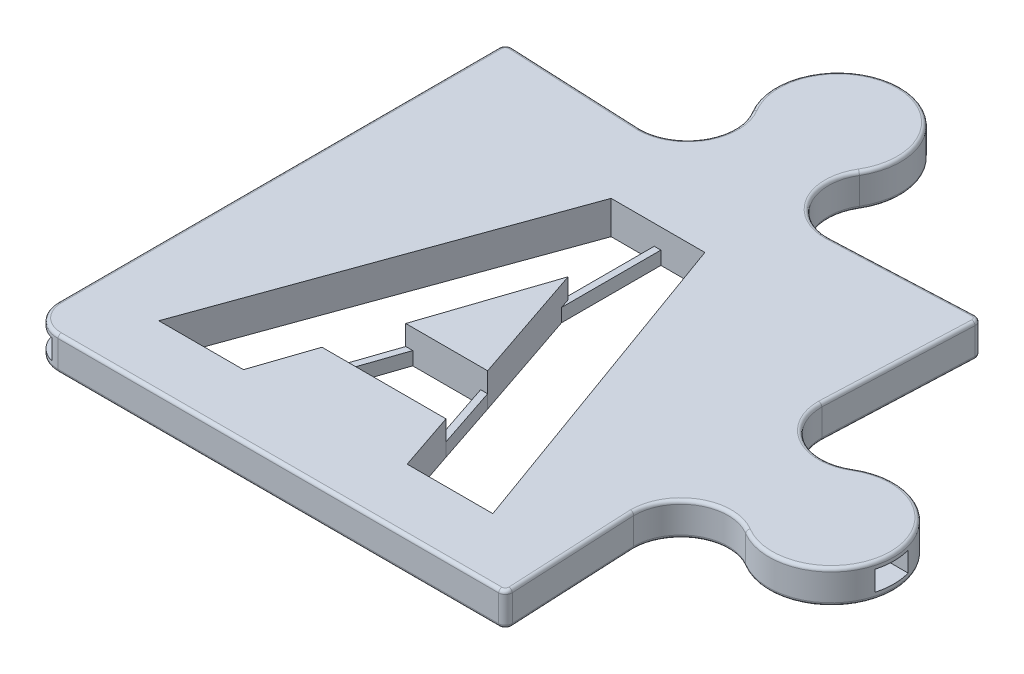
SolidWorks part; units mm, degrees
ref_plane "Front Plane" through (0, 0, 0) normal (0, 0, 1) x (1, 0, 0)
ref_plane "Top Plane" through (0, 0, 0) normal (0, 1, 0) x (1, 0, 0)
ref_plane "Right Plane" through (0, 0, 0) normal (1, 0, 0) x (0, 0, -1)
sketch "Sketch1" plane through (0, 0, 0) normal (0, 1, 0) x (1, 0, 0)
  line L0 (-31, -36) -> (37, -36) construction
  line L1 (-36, 37) -> (-36, -31) construction
  line L2 (-14.1421, 36) -> (-36, 37) construction
  line L3 (37, 37) -> (14.1421, 36) construction
  line L4 (36, 13.1421) -> (37, 37) construction
  line L5 (37, -36) -> (36, -15.1421) construction
  line L6 (-35.4, 36.3719) -> (-35.4, -31)
  line L7 (-36, 36) -> (36, 36) construction
  line L8 (-36, 36) -> (-36, -36) construction
  line L9 (-36, -36) -> (36, -36) construction
  line L10 (36, 36) -> (36, -36) construction
  line L11 (-31, -35.4) -> (36.3705, -35.4)
  line L12 (36.3705, -35.4) -> (35.4, -15.1568)
  line L13 (35.4, 13.155) -> (36.3732, 36.372)
  line L14 (36.3732, 36.372) -> (14.1555, 35.4)
  line L15 (-14.1562, 35.4) -> (-35.4, 36.3719)
  line L16 (-30, -24) -> (30, -24) construction
  line L17 (-30, 29) -> (30, 29) construction
  line L18 (-30, 29) -> (-30, -31) construction
  line L19 (-30, -31) -> (30, -31) construction
  line L20 (30, 29) -> (30, -31) construction
  line L21 (-30, 24) -> (30, 24) construction
  line L22 (-30, 24) -> (-30, -26) construction
  line L23 (-30, -26) -> (30, -26) construction
  line L24 (30, 24) -> (30, -26) construction
  arc A0 (-36, -31) -> (-31, -36) centre (-31, -31) ccw construction
  arc A1 (-14.1421, 36) -> (-8.571, 45.8485) centre (-14.1421, 42.5) ccw construction
  arc A2 (8.571, 45.8485) -> (-8.571, 45.8485) centre (0, 51) ccw construction
  arc A3 (8.571, 45.8485) -> (14.1421, 36) centre (14.1421, 42.5) ccw construction
  arc A4 (36, 13.1421) -> (45.8485, 7.571) centre (42.5, 13.1421) ccw construction
  arc A5 (45.8485, -9.571) -> (45.8485, 7.571) centre (51, -1) ccw construction
  arc A6 (45.8485, -9.571) -> (36, -15.1421) centre (42.5, -15.1421) ccw construction
  arc A7 (-35.4, -31) -> (-31, -35.4) centre (-31, -31) ccw
  arc A8 (46.1576, -9.0567) -> (35.4, -15.1568) centre (42.5, -15.1421) ccw
  arc A9 (46.1576, -9.0567) -> (46.1576, 7.0567) centre (51, -1) ccw
  arc A10 (35.4, 13.155) -> (46.1576, 7.0567) centre (42.5, 13.1421) ccw
  arc A11 (8.0567, 46.1576) -> (14.1555, 35.4) centre (14.1421, 42.5) ccw
  arc A12 (8.0567, 46.1576) -> (-8.0567, 46.1576) centre (0, 51) ccw
  arc A13 (-14.1562, 35.4) -> (-8.0567, 46.1576) centre (-14.1421, 42.5) ccw
  point P32 (36, 0)
  point P34 (0, 36)
  dimension "D5" = 6.5
  dimension "D6" = 10
  dimension "D7" = 6.5
  dimension "D13" = 5
  dimension "D9" = 10
  dimension "D11" = 6.5
  dimension "D12" = 6.5
  dimension "D1" = 72
  dimension "D2" = 1
  dimension "D3" = 1
  dimension "D4" = 15
  dimension "D8" = 1
  dimension "D10" = 35
  dimension "D14" = 15
  dimension "D15" = 36
  dimension "D16" = 1
  dimension "D18" = 60
  dimension "D19" = 60
  dimension "D20" = 5
  dimension "D21" = 6
  dimension "D22" = 5
  dimension "D23" = 50
  dimension "D24" = 2
  dimension "D17" = 0.6
extrude "Boss-Extrude1" add sketch "Sketch1" along normal blind 5
sketch "Sketch6" plane through (0, 0, 0) normal (0, -1, 0) x (1, 0, 0)
  line L0 (-35.4, -36.3719) -> (-35.4, 31) construction
  line L1 (-35.4, 17.9) -> (-27.4, 17.9)
  line L2 (-35.4, 17.9) -> (-35.4, -16.1)
  line L3 (-35.4, -16.1) -> (-27.4, -16.1)
  line L4 (-27.4, 17.9) -> (-27.4, -16.1)
  line L5 (-31, 35.4) -> (36.3705, 35.4) construction
  line L6 (-35.4, 14.65) -> (-30.4, 14.65)
  line L7 (-35.4, 14.65) -> (-35.4, -12.85)
  line L8 (-35.4, -12.85) -> (-30.4, -12.85)
  line L9 (-30.4, 14.65) -> (-30.4, -12.85)
  point P15 (-27.4, 0.9)
  point P16 (-30.4, 0.9)
  line M28 (-35.4, 31) -> (-35.4, -36.3719)
  dimension "D1" = 8
  dimension "D2" = 20.75
  dimension "D3" = 27.5
  dimension "D4" = 5
  dimension "D5" = 34
extrude "Cut-Extrude3" cut sketch "Sketch6" against normal blind 3 from offset 1 contours L6 L9 L8 L3 L4 L1 M28 | L9 L6 L2 L8 region at (-29.8665, 0, 0.9) region at (-32.9, 0, 0.9) offset against normal yes
extrude "Cut-Extrude4" cut sketch "Sketch6<3>" against normal up to next contours L9 L6 L2 L8 region at (-32.9, 0, 0.9)
sketch "Sketch6<3>" plane through (0, 0, 0) normal (0, -1, 0) x (1, 0, 0) same geometry as "Sketch6"
sketch "Sketch8" plane through (0, 0, 0) normal (0, -1, 0) x (1, 0, 0)
  line L1 (-2.5, -51.4) -> (2.5, -51.4)
  line L2 (-2.5, -51.4) -> (-2.5, -60.4)
  line L3 (-2.5, -60.4) -> (2.5, -60.4)
  line L4 (2.5, -51.4) -> (2.5, -60.4)
  line L5 (51.4, 3.5) -> (60.4, 3.5)
  line L6 (51.4, 3.5) -> (51.4, -1.5)
  line L7 (51.4, -1.5) -> (60.4, -1.5)
  line L8 (60.4, 3.5) -> (60.4, -1.5)
  arc A0 (-8.0567, -46.1576) -> (8.0567, -46.1576) centre (0, -51) ccw construction
  arc A1 (46.1576, -7.0567) -> (46.1576, 9.0567) centre (51, 1) ccw construction
  point P4 (0, -60.4)
  point P13 (60.4, 1)
  dimension "D1" = 5
  dimension "D2" = 9
  dimension "D3" = 5
  dimension "D4" = 9
extrude "Cut-Extrude5" cut sketch "Sketch8" against normal blind 3 from offset 1 offset against normal yes
sketch "Sketch9" plane through (0, 0, 0) normal (0, -1, 0) x (1, 0, 0)
  line L0 (-31, 35.4) -> (36.3705, 35.4) construction
  line L1 (-35.4, 14.65) -> (-35.4, 31) construction
  line L2 (-31.7636, 35.3332) -> (-35.4, 31) construction
  line L3 (-33.2571, 29.735) -> (-30.0429, 33.565) construction
  line L4 (-30.0429, 33.565) -> (-33.2571, 29.735) construction
  line L5 (-30.0429, 33.565) -> (-32.7119, 35.8048)
  line L6 (-33.2571, 29.735) -> (-35.926, 31.9747)
  line L7 (-32.7119, 35.8048) -> (-35.926, 31.9747)
  circle A0 centre (-31.65, 31.65) radius 2.5
  arc A1 (-31, 35.4) -> (-35.4, 31) centre (-31, 31) ccw construction
  arc M41 (-31, 35.4) -> (-35.4, 31) centre (-31, 31) ccw
  dimension "D1" = 5
  dimension "D3" = 3.75
  dimension "D4" = 5.6569
  dimension "D2" = 3.75
extrude "Cut-Extrude6" cut sketch "Sketch9" against normal blind 3 from offset 1 contours A0 L5 L6 M41 | A0 L5 region at (-33.6239, 0, 33.3064) region at (-31.65, 0, 31.65) offset against normal yes
sketch "Sketch11" plane through (-35.4, 0, 0) normal (-1, 0, 0) x (0, 0, 1)
  line L0 (-13.155, 0) -> (-36.372, 0) construction
  line L1 (-25.1, 3) -> (-19.1, 3)
  line L2 (-25.1, 3) -> (-25.1, 1.5)
  line L3 (-25.1, 1.5) -> (-19.1, 1.5)
  line L4 (-19.1, 3) -> (-19.1, 1.5)
  line L5 (-16.1, 4) -> (-16.1, 1) construction
  line L6 (35.4, 0) -> (15.1568, 0) construction
  line L7 (20.9, 3) -> (26.9, 3)
  line L8 (20.9, 3) -> (20.9, 1.5)
  line L9 (20.9, 1.5) -> (26.9, 1.5)
  line L10 (26.9, 3) -> (26.9, 1.5)
  line L12 (17.9, 4) -> (17.9, 1) construction
  dimension "D1" = 3
  dimension "D2" = 1.5
  dimension "D3" = 3
  dimension "D4" = 6
  dimension "D5" = 3
  dimension "D6" = 1.5
  dimension "D7" = 6
  dimension "D8" = 3
fillet "Fillet1" radius 0.5 17 edges at (-35.4, 0, 22.825) (-34.1113, 0, 34.1113) (2.6853, 0, 35.4) (35.8853, 0, 25.2784) (38.9978, 0, 8.966) (60.4, 0, 1) (38.9986, 0, -6.9655) (35.8866, 0, -24.7635) (25.2643, 0, -35.886) (7.9657, 0, -38.9984) (0, 0, -60.4) (-7.9658, 0, -38.9981) (-24.7781, 0, -35.886) (-35.4, 0, -24.611) (-32.9, 0, -12.85) (-30.4, 0, 0.9) (-32.9, 0, 14.65)
fillet "Fillet2" radius 0.5 13 edges at (-7.9658, 5, -38.9981) (0, 5, -60.4) (7.9657, 5, -38.9984) (25.2643, 5, -35.886) (35.8866, 5, -24.7635) (38.9986, 5, -6.9655) (60.4, 5, 1) (38.9978, 5, 8.966) (35.8853, 5, 25.2784) (2.6853, 5, 35.4) (-34.1113, 5, 34.1113) (-35.4, 5, -2.686) (-24.7781, 5, -35.886)
fillet "Fillet3" radius 1 9 edges at (36.2202, 0.1464, -36.2187) (36.2202, 4.8536, -36.2187) (36.3732, 2.5, -36.372) (-35.2536, 0.1464, -36.2186) (-35.2536, 4.8536, -36.2186) (36.2169, 0.1464, 35.2536) (36.2169, 4.8536, 35.2536) (36.3705, 2.5, 35.4) (-35.4, 2.5, -36.3719)
extrude "Cut-Extrude9" cut sketch "Sketch11" against normal blind 3
chamfer "Chamfer1" distance 1 angle 50 2 edges at (-35.4, 1.5, 23.9) (-35.4, 1.5, -22.1) first distance on face at (-35.4, 2.25, -22.1)
sketch "Sketch12" plane through (0, 5, 0) normal (0, 1, 0) x (1, 0, 0)
  text T0 "A" font "Poppins" height 50
extrude "Cut-Extrude10" cut sketch "Sketch12" against normal blind 10
sketch "Sketch13" plane through (0, 0, 0) normal (0, -1, 0) x (1, 0, 0)
  line L0 (-0.1649, -10.5416) -> (-6.2964, 7.7704) construction
  line L1 (-0.6624, -9.0558) -> (0.3376, -9.0558)
  line L2 (-0.6624, -9.0558) -> (-0.6624, -24)
  line L3 (-0.6624, -24) -> (0.3376, -24)
  line L4 (0.3376, -9.0558) -> (0.3376, -24)
  line L5 (-30, -24) -> (30, -24) construction
  line L6 (-9.5012, 17.1686) -> (-12.4897, 26) construction
  line L7 (-25.237, 26) -> (-12.1513, 26)
  line L8 (-25.237, 26) -> (-25.237, 25)
  line L9 (-25.237, 25) -> (-12.1513, 25)
  line L10 (-12.1513, 26) -> (-12.1513, 25)
  line L11 (12.1496, 26) -> (9.1612, 17.1686) construction
  line L12 (25.0412, 26) -> (11.8112, 26)
  line L13 (25.0412, 26) -> (25.0412, 25)
  line L14 (25.0412, 25) -> (11.8112, 25)
  line L15 (11.8112, 26) -> (11.8112, 25)
  line L16 (-9.5012, 17.1686) -> (-6.2964, 7.7704)
  line L17 (-6.2964, 7.7704) -> (-5.2398, 7.7704)
  line L18 (-6.2964, 7.7704) -> (6.0284, 7.7704) construction
  line L19 (-5.2398, 7.7704) -> (-8.4447, 17.1686)
  line L20 (9.1612, 17.1686) -> (-9.5012, 17.1686) construction
  line L21 (-8.4447, 17.1686) -> (-9.5012, 17.1686)
  line L22 (9.1612, 17.1686) -> (6.0284, 7.7704)
  line L23 (6.0284, 7.7704) -> (4.9743, 7.7704)
  line L24 (4.9743, 7.7704) -> (8.1071, 17.1686)
  line L25 (8.1071, 17.1686) -> (9.1612, 17.1686)
  line L26 (6.0284, 7.7704) -> (-0.1649, -10.5416) construction
  dimension "D1" = 1
  dimension "D2" = 1
  dimension "D3" = 1
  dimension "D4" = 1
  dimension "D5" = 1
extrude "Boss-Extrude2" add sketch "Sketch13" against normal blind 2
